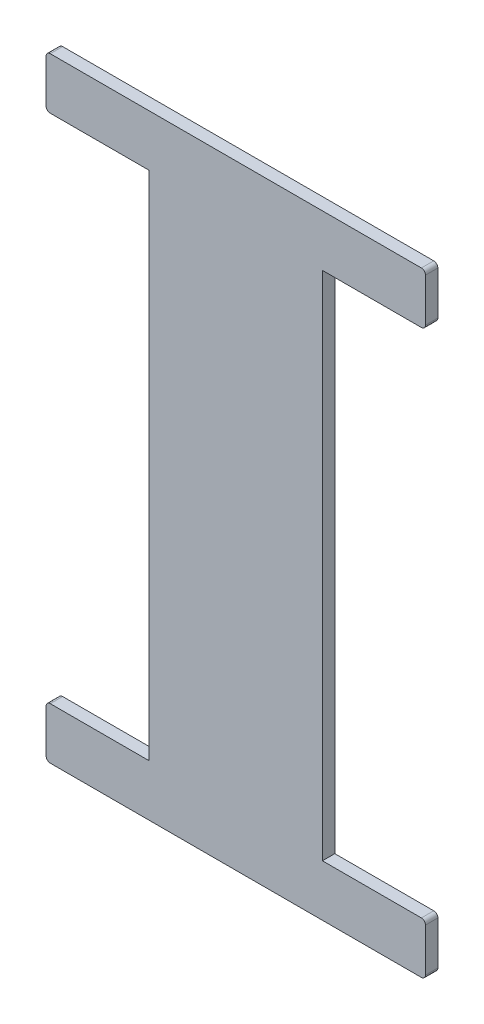
SolidWorks part; units mm, degrees
material "ABS"
ref_plane "前视基准面" through (0, 0, 0) normal (0, 0, 1) x (1, 0, 0)
ref_plane "上视基准面" through (0, 0, 0) normal (0, 1, 0) x (1, 0, 0)
ref_plane "右视基准面" through (0, 0, 0) normal (1, 0, 0) x (0, 0, -1)
other "Configuration Table"
sketch "草图1" plane through (0, 0, 0) normal (0, 0, 1) x (1, 0, 0)
  line L0 (-70.5706, 0) -> (16.54, 0) construction
  line L1 (0, 30.2544) -> (0, -24.4654) construction
  line L3 (-21, -74.5) -> (21, -74.5)
  line L4 (-21, -74.5) -> (-21, 74.5)
  line L5 (-21, 74.5) -> (21, 74.5)
  line L6 (21, -74.5) -> (21, 74.5)
  line L7 (-21, -74.5) -> (21, 74.5) construction
  line L8 (-21, 74.5) -> (21, -74.5) construction
  point P4 (0, 0)
  dimension "D1" = 149
  dimension "D2" = 42
extrude "凸台-拉伸1" add sketch "草图1" along normal blind 3
sketch "草图2" plane through (0, 0, 3) normal (0, 0, 1) x (1, 0, 0)
  line L0 (-50.6483, 0) -> (69.5569, 0) construction
  line L1 (21, -74.5) -> (46, -74.5)
  line L2 (21, -74.5) -> (21, -62)
  line L3 (21, -62) -> (46, -62)
  line L4 (46, -74.5) -> (46, -62)
  line L5 (0, 90.4915) -> (0, -100.3961) construction
  line L6 (-46, -74.5) -> (-46, -62)
  line L7 (-21, -62) -> (-46, -62)
  line L8 (-21, -74.5) -> (-21, -62)
  line L9 (-21, -74.5) -> (-46, -74.5)
  line L10 (-21, 74.5) -> (-46, 74.5)
  line L11 (-21, 74.5) -> (-21, 62)
  line L12 (-21, 62) -> (-46, 62)
  line L13 (-46, 74.5) -> (-46, 62)
  line L14 (46, 74.5) -> (46, 62)
  line L15 (21, 62) -> (46, 62)
  line L16 (21, 74.5) -> (21, 62)
  line L17 (21, 74.5) -> (46, 74.5)
  dimension "D1" = 12.5
  dimension "D2" = 25
extrude "凸台-拉伸2" add sketch "草图2" against normal up to surface (3 mm away) up to face at (0, 0, 0)
fillet "圆角1" radius 1 8 edges at (46, 74.5, 1.5) (46, 62, 1.5) (46, -62, 1.5) (46, -74.5, 1.5) (-46, -74.5, 1.5) (-46, -62, 1.5) (-46, 74.5, 1.5) (-46, 62, 1.5)
